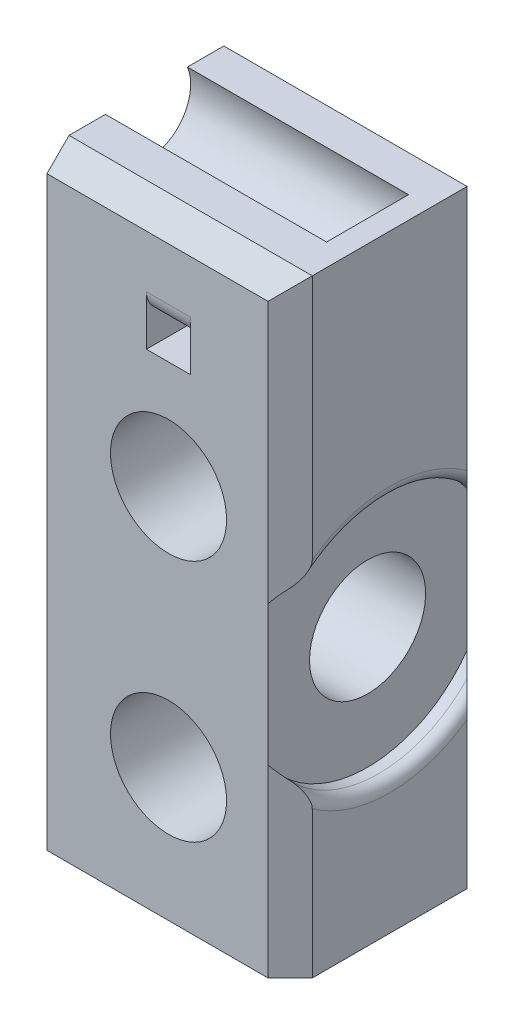
SolidWorks part; units mm, degrees
material "ABS generico"
ref_plane "Piano frontale" through (0, 0, 0) normal (0, 0, 1) x (1, 0, 0)
ref_plane "Piano superiore" through (0, 0, 0) normal (0, 1, 0) x (1, 0, 0)
ref_plane "Piano destro" through (0, 0, 0) normal (1, 0, 0) x (0, 0, -1)
sketch "Sketch1" plane through (0, 0, 0) normal (0, 0, 1) x (1, 0, 0)
  line L0 (0, 0) -> (0, 55)
  line L1 (0, 55) -> (22, 55)
  line L2 (22, 55) -> (22, 0)
  line L3 (22, 0) -> (0, 0)
  line L4 (11, 55) -> (11, 0) construction
  line L6 (13, 43.75) -> (9, 43.75)
  line L7 (13, 43.75) -> (13, 46.25)
  line L8 (13, 46.25) -> (9, 46.25)
  line L9 (9, 43.75) -> (9, 46.25)
  line L10 (13, 43.75) -> (9, 46.25) construction
  line L11 (13, 46.25) -> (9, 43.75) construction
  circle A0 centre (11, 12) radius 5.25
  circle A1 centre (11, 34) radius 5.25
  point P11 (11, 45)
  dimension "D5" = 10.5
  dimension "D1" = 22
  dimension "D2" = 55
  dimension "D3" = 12
  dimension "D4" = 34
  dimension "D6" = 10
  dimension "D7" = 4
  dimension "D8" = 2.5
extrude "Boss-Extrude1" add sketch "Sketch1" against normal blind 18
sketch "Sketch2" plane through (0, 0, 0) normal (-1, 0, 0) x (0, 0, 1)
  line L0 (-9, 0) -> (-9, 55) construction
  line L1 (-18, 0) -> (0, 0) construction
  line L2 (-18, 55) -> (0, 55) construction
  circle A0 centre (-9, 23) radius 5.25
  dimension "D2" = 10.5
  dimension "D1" = 23
extrude "Cut-Extrude1" cut sketch "Sketch2" against normal through all
sketch "Sketch3" plane through (0, 0, 0) normal (1, 0, 0) x (0, 0, -1)
  line L0 (9, 55) -> (9, 62.8182) construction
  line L2 (18, 55) -> (0, 55) construction
  circle A0 centre (9, 53.5) radius 4
  dimension "D1" = 8
  dimension "D2" = 1.5
extrude "Cut-Extrude2" cut sketch "Sketch3" along normal blind 20
chamfer "Chamfer1" distance 2 angle 45 2 edges at (22, 27.5, 0) (22, 27.5, -18)
sketch "Sketch4" plane through (22, 0, 0) normal (1, 0, 0) x (0, 0, -1)
  circle A0 centre (9, 23) radius 11
  dimension "D1" = 22
extrude "Cut-Extrude3" cut sketch "Sketch4" against normal blind 2
fillet "Fillet1" radius 1 2 edges at (22, 34, -9) (22, 12, -9)
chamfer "Chamfer2" distance 2 angle 45 2 edges at (10, 55, 0) (10, 55, -18)
fillet "Fillet2" radius 2 2 edges at (11, 46.25, -18) (11, 46.25, 0)
